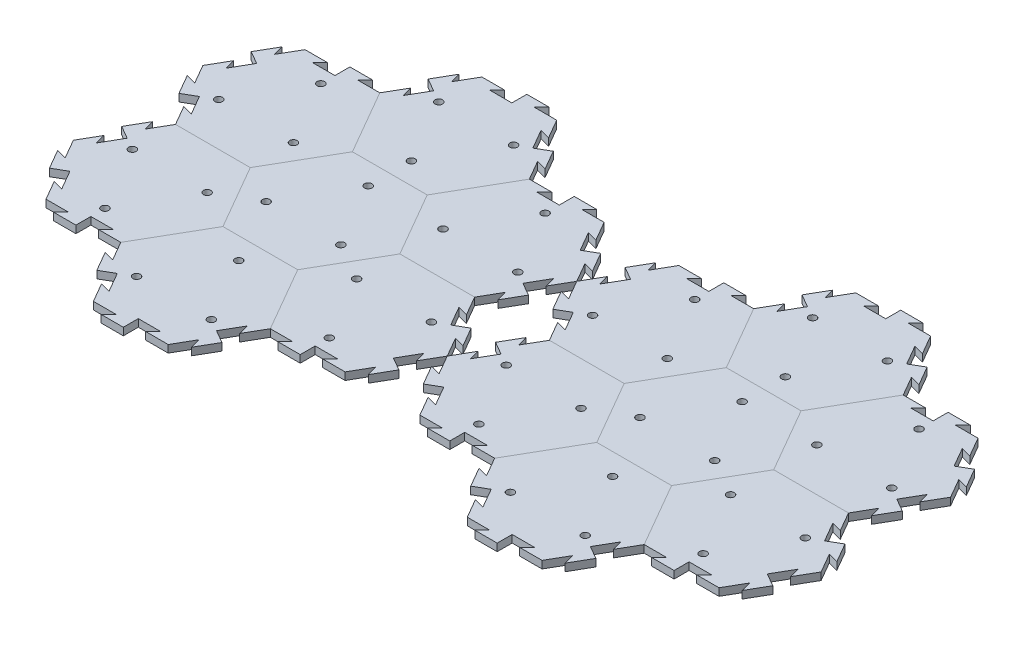
SolidWorks part; units mm, degrees
note: '?' marks a value the reader was unsure of.
material "Cedar"
ref_plane "Front Plane" through (0, 0, 0) normal (0, 0, 1) x (1, 0, 0)
ref_plane "Top Plane" through (0, 0, 0) normal (0, 1, 0) x (1, 0, 0)
ref_plane "Right Plane" through (0, 0, 0) normal (1, 0, 0) x (0, 0, -1)
sketch "Sketch1" plane through (0, 0, 0) normal (0, 1, 0) x (1, 0, 0)
  line L0 (0, 0) -> (63.5, 0) construction
  line L1 (63.5, 0) -> (31.75, 54.9926)
  line L2 (31.75, 54.9926) -> (-31.75, 54.9926)
  line L3 (-31.75, 54.9926) -> (-63.5, 0)
  line L4 (-63.5, 0) -> (-31.75, -54.9926)
  line L5 (-31.75, -54.9926) -> (31.75, -54.9926)
  line L6 (31.75, -54.9926) -> (63.5, 0)
  circle A0 centre (0, 0) radius 54.9926 construction
  dimension "D1" = 63.5
extrude "Boss-Extrude1" add sketch "Sketch1" against normal blind 6.35
sketch "Sketch2" plane through (0, 0, 0) normal (0, 1, 0) x (1, 0, 0)
  point P1 (0, 0)
ref_axis "Axis1" through (0, 0, 0) along (0, 1, 0)?
sketch "Sketch9" plane through (0, 0, 0) normal (0, 1, 0) x (1, 0, 0)
  line L1 (31.75, -18.3309) -> (0, 36.6617) construction
  line L2 (0, 36.6617) -> (-31.75, -18.3309) construction
  line L3 (-31.75, -18.3309) -> (31.75, -18.3309) construction
  circle A0 centre (0, 0) radius 18.3309 construction
  circle A1 centre (-31.75, -18.3309) radius 3.175
  dimension "D2" = 6.35
  dimension "D1" = 63.5
extrude "Cut-Extrude3" cut sketch "Sketch9" against normal through all
pattern_circular "CirPattern6" count 3 over 360 about axis through (0, 0, 0) along (0, 1, 0) of "Cut-Extrude3"
mirror "Mirror1" about plane through (31.75, -6.35, 54.9926) normal (0.866, 0, 0.5) of bodies 121 101
sketch "Sketch5" plane through (0, 0, 0) normal (0, 1, 0) x (1, 0, 0)
  line L0 (127, 0) -> (136.525, -16.4978) construction
  line L1 (127, 0) -> (158.75, -54.9926) construction
  line L2 (136.525, -16.4978) -> (127.8507, -14.1735)
  line L3 (127.8507, -14.1735) -> (137.3757, -30.6713)
  line L4 (137.3757, -30.6713) -> (142.875, -27.4963)
  line L5 (127, 0) -> (158.75, -54.9926) construction
  line L6 (136.525, -16.4978) -> (142.875, -27.4963)
  dimension "D1" = 45
  dimension "D2" = 6.35
sketch "Sketch6" plane through (0, 0, 0) normal (0, 1, 0) x (1, 0, 0)
  line L0 (31.75, -54.9926) -> (158.75, -54.9926) construction
  point P4 (95.25, -54.9926)
ref_axis "Axis3" through (95.25, 0, 54.9926) along (0, 1, 0)?
extrude "Cut-Extrude2" cut sketch "Sketch5" against normal through all
sketch "Sketch7" plane through (0, 0, 0) normal (0, 1, 0) x (1, 0, 0)
  line L0 (142.875, -27.4963) -> (158.75, -54.9926) construction
  line L1 (142.875, -27.4963) -> (158.75, -54.9926) construction
  line L2 (142.875, -27.4963) -> (148.3743, -24.3213)
  line L3 (148.3743, -24.3213) -> (157.8993, -40.8191)
  line L4 (157.8993, -40.8191) -> (149.225, -38.4948)
  line L5 (149.225, -38.4948) -> (142.875, -27.4963)
  line L6 (149.225, -38.4948) -> (158.75, -54.9926) construction
  line L7 (149.225, -38.4948) -> (158.75, -54.9926) construction
  dimension "D1" = 45
  dimension "D2" = 6.35
extrude "Boss-Extrude3" add sketch "Sketch7" against normal up to surface (6.35 mm away) up to face at (63.5, -6.35, 33.4867)
pattern_circular "CirPattern3" count 3 every 60 about axis through (95.25, 0, 54.9926) along (0, 1, 0) of "Cut-Extrude2", "Boss-Extrude3"
pattern_circular "CirPattern5" count 6 over 360 about axis through (0, 0, 0) along (0, 1, 0) of bodies 113
pattern_linear "LPattern1" count 2 spacing 317.5 along (1, 0, 0) of bodies 115 113 119 121 118 116 117
